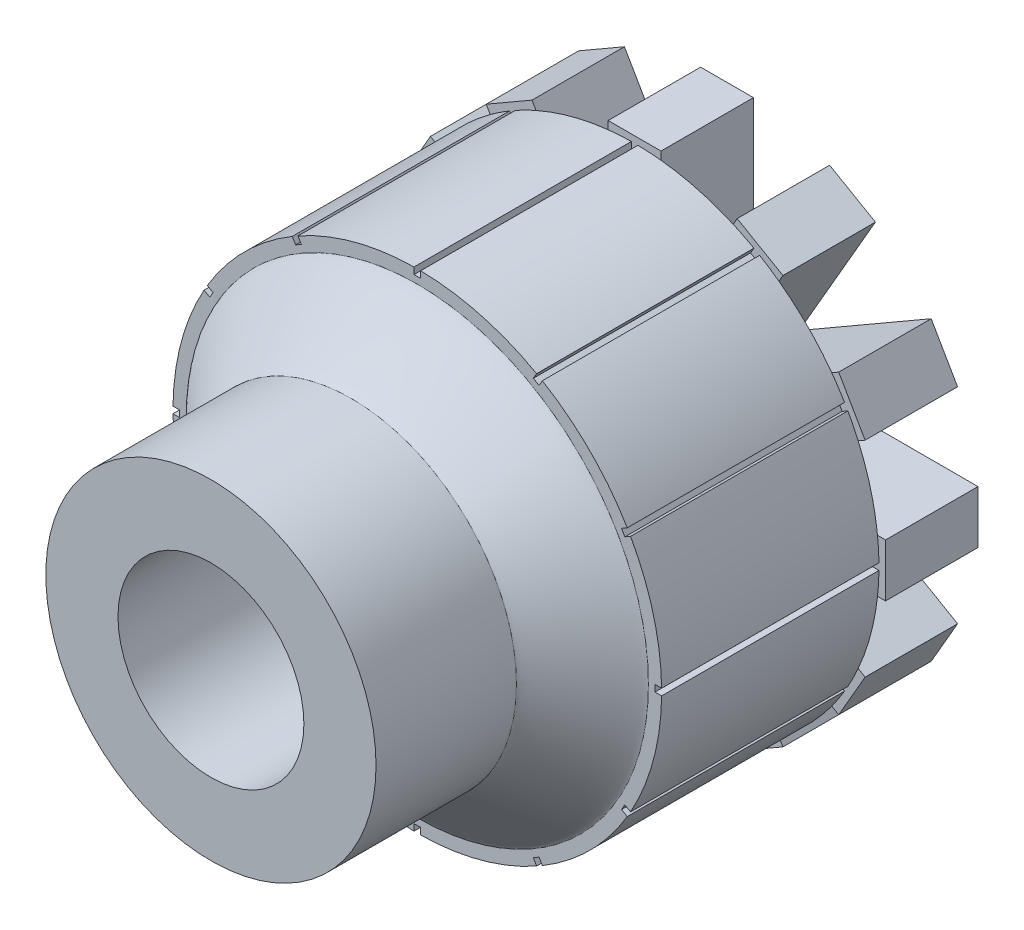
SolidWorks part; units mm, degrees
ref_plane "Front Plane" through (0, 0, 0) normal (0, 0, 1) x (1, 0, 0)
ref_plane "Top Plane" through (0, 0, 0) normal (0, 1, 0) x (1, 0, 0)
ref_plane "Right Plane" through (0, 0, 0) normal (1, 0, 0) x (0, 0, -1)
sketch "Sketch1" plane through (0, 0, 0) normal (0, 0, 1) x (1, 0, 0)
  circle A0 centre (0, 0) radius 9.398
  dimension "D1" = 18.796
extrude "Boss-Extrude1" add sketch "Sketch1" along normal blind 16.2941
sketch "Sketch2" plane through (0, 0, 16.2941) normal (0, 0, 1) x (1, 0, 0)
  circle A0 centre (0, 0) radius 6.35
extrude "Cut-Extrude1" cut sketch "Sketch2" against normal blind 7.9375 flip side to cut
fillet "Fillet1" radius 2.54 1 edges at (6.35, 0, 8.3566) conic radius 37.94
sketch "Sketch3" plane through (0, 0, 0) normal (0, 0, -1) x (-1, 0, 0)
  line L1 (-9.652, -1.016) -> (9.652, -1.016)
  line L2 (-9.652, -1.016) -> (-9.652, 1.016)
  line L3 (-9.652, 1.016) -> (9.652, 1.016)
  line L4 (9.652, -1.016) -> (9.652, 1.016)
  line L5 (-9.652, -1.016) -> (9.652, 1.016) construction
  line L6 (-9.652, 1.016) -> (9.652, -1.016) construction
  point P0 (0, 0)
  dimension "D1" = 2.032
  dimension "D2" = 19.304
extrude "Boss-Extrude2" add sketch "Sketch3" along normal blind 3.556
pattern_circular "CirPattern1" count 12 over 360 about axis through (0, 0, 0) along (0, 0, 1) of "Boss-Extrude2"
sketch "Sketch5" plane through (0, 0, 0) normal (1, 0, 0) x (0, 0, -1)
  line L0 (0, 1.016) -> (0, -1.016) construction
  line L1 (-10.16, 0.127) -> (0, 0.127)
  line L3 (-10.16, 0.127) -> (-10.16, -0.127)
  line L4 (-10.16, -0.127) -> (0, -0.127)
  line L5 (0, 0.127) -> (0, -0.127)
  line L6 (-10.16, 0.127) -> (0, -0.127) construction
  line L7 (-10.16, -0.127) -> (0, 0.127) construction
  point P0 (-5.08, 0)
  dimension "D1" = 10.16
  dimension "D2" = 0.254
extrude "Cut-Extrude2" cut sketch "Sketch5" along normal blind 0.254 from offset 9.398 offset against normal yes
pattern_circular "CirPattern2" count 12 over 360 about axis through (0, 0, 16.2941) along (0, 0, -1) of "Cut-Extrude2"
sketch "Sketch6" plane through (0, 0, 16.2941) normal (0, 0, 1) x (1, 0, 0)
  circle A0 centre (0, 0) radius 3.575
  dimension "D1" = 7.1501
extrude "Cut-Extrude3" cut sketch "Sketch6" against normal through all both and the other way through all
